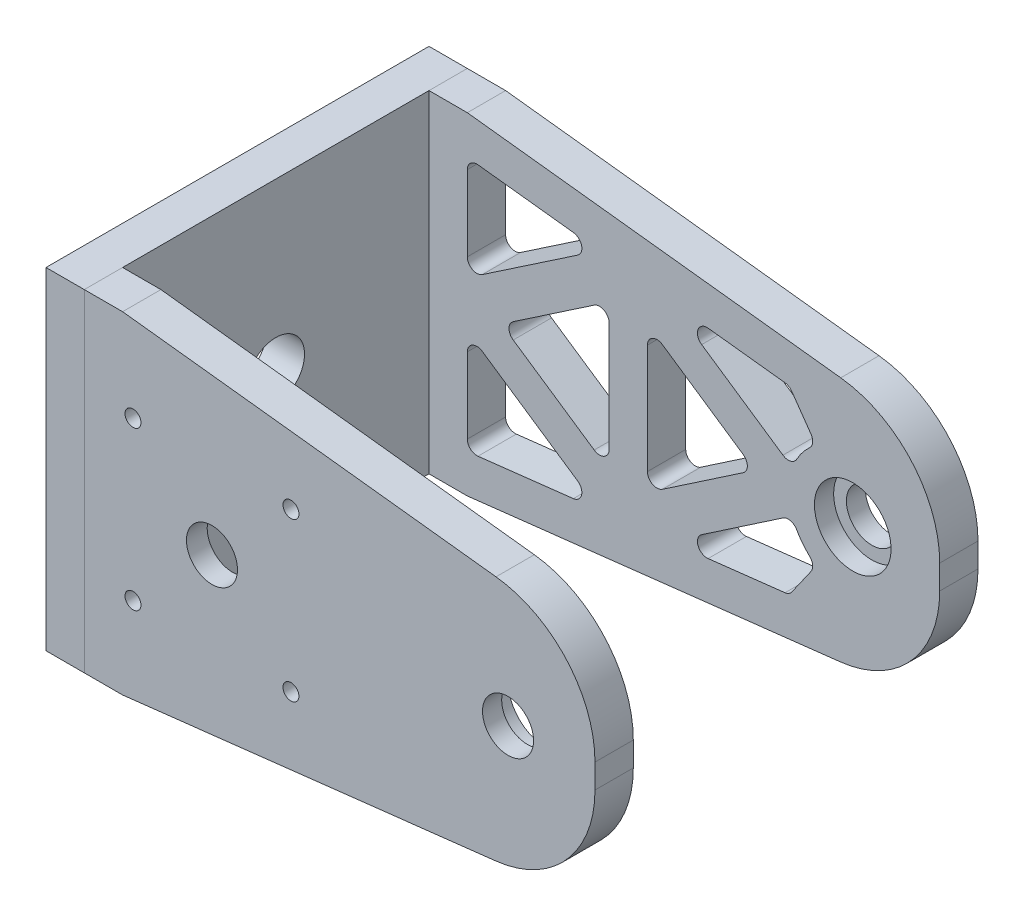
SolidWorks part; units mm, degrees
material "6061 Alloy"
ref_plane "Front Plane" through (0, 0, 0) normal (1, 0, 0) x (0, 1, 0)
ref_plane "Top Plane" through (0, 0, 0) normal (0, 0, 1) x (0, 1, 0)
ref_plane "Right Plane" through (0, 0, 0) normal (0, 1, 0) x (-1, 0, 0)
ref_axis "Axis1" through (0, -88.99, 0) along (0, 1, 0)
ref_axis "Axis2" through (55, 0, 0) along (-1, 0, 0)
sketch "Sketch1" plane through (0, 0, 0) normal (1, 0, 0) x (0, 1, 0)
  line L1 (-52, 60) -> (52, 60)
  line L2 (-52, 60) -> (-52, -60)
  line L3 (-52, -60) -> (52, -60)
  line L4 (52, 60) -> (52, -60)
  line L5 (-52, 60) -> (52, -60) construction
  line L6 (-52, -60) -> (52, 60) construction
  circle A0 centre (0, 0) radius 9
  point P0 (0, 0)
  dimension "D3" = 18
  dimension "D1" = 120
  dimension "D2" = 104
extrude "Boss-Extrude1" add sketch "Sketch1" along normal blind 12
sketch "Sketch2" plane through (12, 0, 0) normal (1, 0, 0) x (0, 1, 0)
  line L1 (-52, 60) -> (52, 60)
  line L2 (-52, 60) -> (-52, 48)
  line L3 (-52, 48) -> (52, 48)
  line L4 (52, 60) -> (52, 48)
  line L5 (-52, 60) -> (52, 48) construction
  line L6 (-52, 48) -> (52, 60) construction
  line L7 (52, -60) -> (52, 60) construction
  point P4 (0, 54)
  dimension "D1" = 12
extrude "Boss-Extrude3" add sketch "Sketch2" along normal blind 160 separate body
mirror "Mirror2" about plane through (0, 0, 0) normal (0, 0, 1) of bodies 104
sketch "Sketch3" plane through (0, 0, 48) normal (0, 0, -1) x (1, 0, 0)
  line L0 (-66, 0) -> (66, 0) construction
  line L1 (55, 0) -> (-55, 0) construction
  line L2 (12, -52) -> (12, 52) construction
  line L3 (17, 35) -> (87, 35)
  line L4 (17, 35) -> (17, -35)
  line L5 (17, -35) -> (87, -35)
  line L6 (87, 35) -> (87, -35)
  line L7 (17, 35) -> (87, -35) construction
  line L8 (17, -35) -> (87, 35) construction
  circle A0 centre (52, 0) radius 8
  circle A1 centre (52, 0) radius 25
  circle A2 centre (52, 0) radius 35 construction
  circle A3 centre (27.2513, 24.7487) radius 2.5
  circle A4 centre (76.7487, 24.7487) radius 2.5
  circle A5 centre (76.7487, -24.7487) radius 2.5
  circle A6 centre (27.2513, -24.7487) radius 2.5
  circle A7 centre (144.7635, 0) radius 12
  circle A8 centre (144.7635, 0) radius 8
  dimension "D1" = 16
  dimension "D2" = 50
  dimension "D3" = 70
  dimension "D6" = 5
  dimension "D8" = 24
  dimension "D9" = 16
  dimension "D4" = 70
  dimension "D5" = 40
  dimension "D7" = 4
extrude "Cut-Extrude1" cut sketch "Sketch3" against normal blind 20 contours A3 | A4 | A6 | A5 | A0
extrude "Cut-Extrude2" cut sketch "Sketch3<3>" against normal blind 5.5 contours A1
sketch "Sketch3<3>" plane through (0, 0, 48) normal (0, 0, -1) x (1, 0, 0) same geometry as "Sketch3"
extrude "Cut-Extrude3" cut sketch "Sketch3<4>" against normal blind 2 contours L3 L6 L5 L4
sketch "Sketch3<4>" plane through (0, 0, 48) normal (0, 0, -1) x (1, 0, 0) same geometry as "Sketch3"
fillet "Fillet1" radius 6 4 edges at (17, 35, 49) (87, 35, 49) (87, -35, 49) (17, -35, 49)
extrude "Cut-Extrude4" cut sketch "Sketch3<5>" against normal through all both and the other way through all contours A8
sketch "Sketch3<5>" plane through (0, 0, 48) normal (0, 0, -1) x (1, 0, 0) same geometry as "Sketch3"
extrude "Cut-Extrude5" cut sketch "Sketch3<6>" against normal blind 6 contours A8 | A7
sketch "Sketch3<6>" plane through (0, 0, 48) normal (0, 0, -1) x (1, 0, 0) same geometry as "Sketch3"
extrude "Cut-Extrude6" cut sketch "Sketch3<7>" along normal blind 6 from surface contours A7 starting at face at (136.7635, 0, -48)
sketch "Sketch3<7>" plane through (0, 0, 48) normal (0, 0, -1) x (1, 0, 0) same geometry as "Sketch3"
sketch "Sketch4" plane through (0, 0, -60) normal (0, 0, -1) x (1, 0, 0)
  line L0 (24, 52) -> (140.994, 38.5615)
  line L1 (172, 52) -> (12, 52) construction
  line L2 (172, -52) -> (172, 52) construction
  line L3 (172, 3.7901) -> (172, 0)
  line L4 (12, 52) -> (12, -52) construction
  line L5 (-66, 0) -> (66, 0) construction
  line L6 (24, -52) -> (140.994, -38.5615)
  line L7 (24, 52) -> (172, 52)
  line L8 (172, 52) -> (172, 3.7901)
  line L9 (172, -3.7901) -> (172, -52)
  line L10 (172, -52) -> (24, -52)
  arc A0 (140.994, 38.5615) -> (172, 3.7901) centre (137, 3.7901) cw
  arc A1 (140.994, -38.5615) -> (172, -3.7901) centre (137, -3.7901) ccw
  point P11 (172, 35)
  dimension "D3" = 35
  dimension "D1" = 35
  dimension "D2" = 12
extrude "Cut-Extrude7" cut sketch "Sketch4" against normal through all both and the other way through all contours L8 L7 L0 A0 | A1 L9 L10 L6
sketch "Sketch5" plane through (0, 0, -60) normal (0, 0, -1) x (1, 0, 0)
  line L0 (29.3531, 3.6223) -> (74.435, 34.1279) construction
  line L1 (119.4182, 3.6247) -> (124.7635, 0) construction
  line L2 (38.378, 2.4846) -> (63.7501, 19.6532)
  line L3 (85.1151, 19.6363) -> (110.4112, 2.483)
  line L4 (28.6813, 10.4123) -> (58.5724, 30.6387)
  line L5 (97.419, 25.7917) -> (122.8844, 8.5236)
  line L6 (131.6604, 18.663) -> (125.6442, 27.2319)
  line L7 (139.6246, 26.6399) -> (124.8699, 28.3347) construction
  line L8 (-66, 0) -> (66, 0) construction
  line L9 (97.419, -25.7917) -> (122.8844, -8.5236)
  line L10 (28.6813, -10.4123) -> (58.5724, -30.6387)
  line L11 (85.1151, -19.6363) -> (110.4112, -2.483)
  line L12 (160, -3.7901) -> (160, 3.7901)
  line L13 (139.6246, 26.6399) -> (24, 39.9211)
  line L14 (24, 39.9211) -> (24, -39.9211)
  line L15 (24, -39.9211) -> (139.6246, -26.6399)
  line L16 (160, -3.7901) -> (160, 3.7901)
  line L17 (123.5313, 28.4884) -> (99.4451, 31.2551)
  line L18 (24, 36.5568) -> (24, 12.8969)
  line L19 (27.3423, -39.5372) -> (57.2335, -36.1037)
  line L20 (27.3625, 4.9692) -> (29.3531, 3.6223) construction
  line L21 (68.4314, 17.1686) -> (68.4314, -17.1686)
  line L22 (74.4314, 26.8809) -> (74.4314, -26.8809) construction
  line L23 (80.4314, 17.1533) -> (80.4314, -17.1533)
  line L24 (68.4314, 26.8809) -> (68.4314, 22.8209) construction
  line L25 (68.4314, 26.8809) -> (68.4314, -26.8809) construction
  line L26 (68.4314, 22.8209) -> (74.4314, 26.8809) construction
  line L27 (27.3625, -4.9692) -> (74.4314, 26.8809) construction
  line L28 (74.4314, 26.8809) -> (80.4314, 22.8123) construction
  line L29 (74.4314, 26.8809) -> (121.3961, -4.9659) construction
  line L30 (80.4314, 26.8809) -> (80.4314, 22.8123) construction
  line L31 (80.4314, 26.8809) -> (80.4314, -26.8809) construction
  line L32 (80.4314, -22.8123) -> (80.4314, -26.8809) construction
  line L33 (74.4314, -26.8809) -> (80.4314, -22.8123) construction
  line L34 (68.4314, -22.8209) -> (74.4314, -26.8809) construction
  line L35 (68.4314, -22.8209) -> (68.4314, -26.8809) construction
  line L36 (27.3625, -4.9692) -> (34.7062, 0) construction
  line L37 (29.3531, 3.6223) -> (34.7062, 0) construction
  line L38 (38.378, -2.4846) -> (63.7501, -19.6532)
  line L39 (114.0728, 0) -> (121.3961, -4.9659) construction
  line L40 (114.0728, 0) -> (119.4182, 3.6247) construction
  line L41 (119.4182, 3.6247) -> (121.3961, 4.9659) construction
  line L42 (74.435, 34.1279) -> (119.4182, 3.6247) construction
  line L43 (74.435, 34.1279) -> (124.7635, 0) construction
  line L44 (24, 0) -> (29.3531, 3.6223) construction
  line L45 (24, 0) -> (74.435, 34.1279) construction
  line L46 (20.6375, 4.9692) -> (24, 7.2446) construction
  line L47 (20.6375, 4.9692) -> (74.4385, 41.3749) construction
  line L48 (20.6375, -4.9692) -> (24, -7.2446) construction
  line L49 (65.2824, -35.1792) -> (74.4385, -41.3749) construction
  line L50 (74.4385, -41.3749) -> (87.3059, -32.6495) construction
  line L51 (74.4385, 41.3749) -> (87.3059, 32.6495) construction
  line L52 (74.4385, 41.3749) -> (128.1309, 4.9659) construction
  line L53 (65.2824, 35.1792) -> (74.4385, 41.3749) construction
  line L54 (125.8529, 6.5107) -> (128.1309, 4.9659) construction
  line L55 (125.8529, -6.5107) -> (128.1309, -4.9659) construction
  line L56 (131.6604, -18.663) -> (125.6442, -27.2319)
  line L57 (124.8699, -28.3347) -> (139.6246, -26.6399) construction
  line L58 (65.2824, -35.1792) -> (87.3059, -32.6495) construction
  line L59 (99.4451, -31.2551) -> (123.5313, -28.4884)
  line L60 (87.3059, 32.6495) -> (74.435, 34.1279) construction
  line L61 (57.2335, 36.1037) -> (27.3423, 39.5372)
  line L62 (74.435, 34.1279) -> (65.2824, 35.1792) construction
  line L63 (24, 0) -> (24, -7.2446) construction
  line L64 (24, -12.8969) -> (24, -36.5568)
  line L65 (24, 7.2446) -> (24, 0) construction
  arc A0 (156.2558, -16.3685) -> (160, -3.7901) centre (137, -3.7901) ccw construction
  arc A1 (133.2713, -16.3685) -> (156.2558, -16.3685) centre (144.7635, 0) ccw construction
  arc A2 (131.2344, 14.7297) -> (127.2023, 9.571) centre (144.7635, 0) ccw
  arc A3 (156.2558, -16.3685) -> (156.2558, 16.3685) centre (144.7635, 0) ccw construction
  arc A4 (160, 3.7901) -> (139.6246, 26.6399) centre (137, 3.7901) ccw
  arc A5 (139.6246, -26.6399) -> (160, -3.7901) centre (137, -3.7901) ccw
  arc A6 (160, 3.7901) -> (156.2558, 16.3685) centre (137, 3.7901) ccw construction
  arc A7 (139.6246, -26.6399) -> (156.2558, -16.3685) centre (137, -3.7901) ccw construction
  arc A8 (156.2558, 16.3685) -> (139.6246, 26.6399) centre (137, 3.7901) ccw construction
  arc A9 (156.2558, 16.3685) -> (133.2713, 16.3685) centre (144.7635, 0) ccw construction
  arc A10 (124.7635, 0) -> (125.8529, -6.5107) centre (144.7635, 0) ccw construction
  arc A11 (127.2023, -9.571) -> (131.2344, -14.7297) centre (144.7635, 0) ccw
  arc A12 (68.4314, 17.1686) -> (63.7501, 19.6532) centre (65.4314, 17.1686) ccw
  arc A13 (38.378, 2.4846) -> (38.378, -2.4846) centre (40.0593, 0) ccw
  arc A14 (63.7501, -19.6532) -> (68.4314, -17.1686) centre (65.4314, -17.1686) ccw
  arc A15 (58.5724, -30.6387) -> (57.2335, -36.1037) centre (56.8911, -33.1233) cw
  arc A16 (24, -36.5568) -> (27.3423, -39.5372) centre (27, -36.5568) ccw
  arc A17 (28.6813, -10.4123) -> (24, -12.8969) centre (27, -12.8969) ccw
  arc A18 (28.6813, 10.4123) -> (24, 12.8969) centre (27, 12.8969) cw
  arc A19 (27.3423, 39.5372) -> (24, 36.5568) centre (27, 36.5568) ccw
  arc A20 (58.5724, 30.6387) -> (57.2335, 36.1037) centre (56.8911, 33.1233) ccw
  arc A21 (97.419, 25.7917) -> (99.4451, 31.2551) centre (99.1027, 28.2747) cw
  arc A22 (125.6442, 27.2319) -> (123.5313, 28.4884) centre (123.1889, 25.508) ccw
  arc A23 (131.6604, 18.663) -> (131.2344, 14.7297) centre (129.2051, 16.9392) cw
  arc A24 (85.1151, 19.6363) -> (80.4314, 17.1533) centre (83.4314, 17.1533) ccw
  arc A25 (110.4112, 2.483) -> (110.4112, -2.483) centre (108.7275, 0) cw
  arc A26 (80.4314, -17.1533) -> (85.1151, -19.6363) centre (83.4314, -17.1533) ccw
  arc A27 (97.419, -25.7917) -> (99.4451, -31.2551) centre (99.1027, -28.2747) ccw
  arc A28 (125.6442, -27.2319) -> (123.5313, -28.4884) centre (123.1889, -25.508) cw
  arc A29 (131.6604, -18.663) -> (131.2344, -14.7297) centre (129.2051, -16.9392) ccw
  arc A30 (122.8844, -8.5236) -> (127.2023, -9.571) centre (124.5681, -11.0066) cw
  arc A31 (125.8529, 6.5107) -> (124.7635, 0) centre (144.7635, 0) ccw construction
  arc A32 (122.8844, 8.5236) -> (127.2023, 9.571) centre (124.5681, 11.0066) ccw
  dimension "D2" = 40
  dimension "D3" = 3
  dimension "D4" = 3
  dimension "D1" = 12
extrude "Cut-Extrude8" cut sketch "Sketch5" against normal blind 20 and the other way through all contours L61 A19 L18 A18 L4 A20 | L21 A14 L38 A13 L2 A12 | L10 A15 L19 A16 L64 A17 | L9 A30 A11 A29 L56 A28 L59 A27 | L11 A25 L3 A24 L23 A26 | L5 A32 A2 A23 L6 A22 L17 A21
